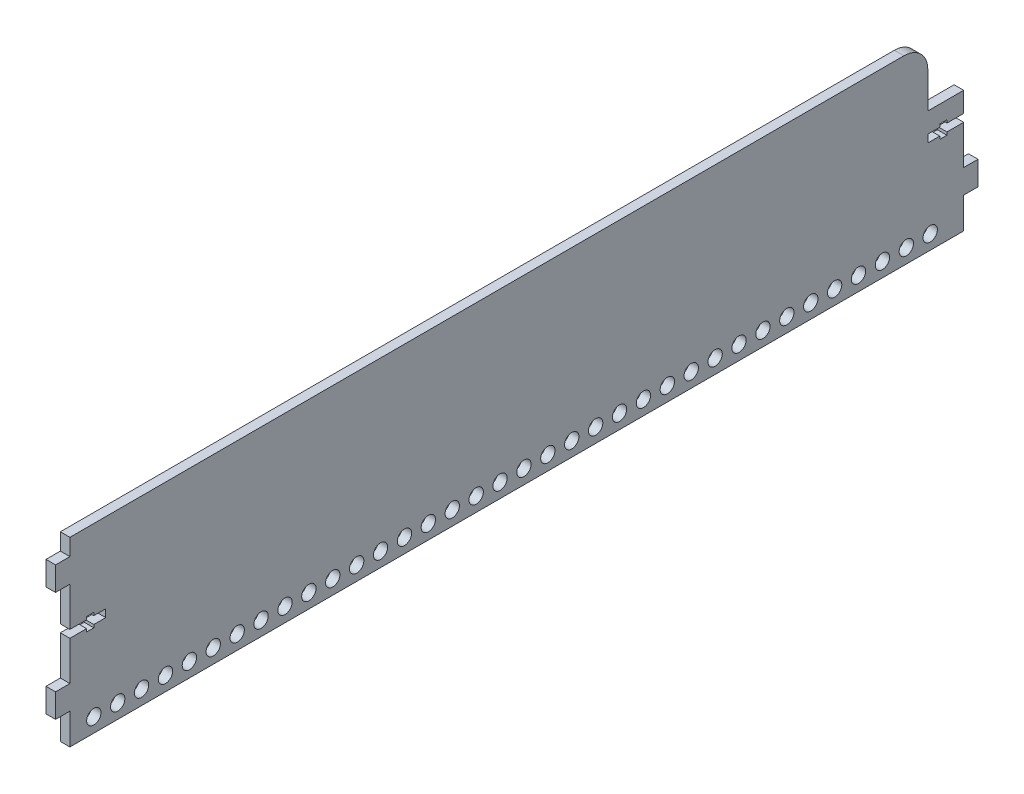
SolidWorks part; units mm, degrees
ref_plane "Front Plane" through (0, 0, 0) normal (0, 0, 1) x (1, 0, 0)
ref_plane "Top Plane" through (0, 0, 0) normal (0, 1, 0) x (1, 0, 0)
ref_plane "Right Plane" through (0, 0, 0) normal (1, 0, 0) x (0, 0, -1)
sketch "Sketch1" plane through (0, 0, 0) normal (1, 0, 0) x (0, 0, -1)
  line L1 (-187, -40) -> (187, -40)
  line L2 (-187, -40) -> (-187, 40)
  line L3 (-187, 40) -> (187, 40)
  line L4 (187, -40) -> (187, 40)
  line L5 (-187, -40) -> (187, 40) construction
  line L6 (-187, 40) -> (187, -40) construction
  point P0 (0, 0)
  dimension "D1" = 80
  dimension "D2" = 374
extrude "Boss-Extrude1" add sketch "Sketch1" along normal blind 4
sketch "Sketch4" plane through (0, 0, 187) normal (0, 0, 1) x (1, 0, 0)
  line L1 (4, 29) -> (0, 29) construction
  line L2 (4, 19) -> (4, 29) construction
  line L3 (0, 29) -> (0, 19) construction
  line L4 (0, 19) -> (4, 19) construction
  line L7 (4, -17) -> (0, -17) construction
  line L8 (4, -27) -> (4, -17) construction
  line L9 (0, -17) -> (0, -27) construction
  line L10 (0, -27) -> (4, -27) construction
  line L13 (4, 29) -> (0, 29)
  line L14 (4, 19) -> (4, 29)
  line L15 (0, 29) -> (0, 19)
  line L16 (0, 19) -> (4, 19)
  line L17 (4, -17) -> (0, -17)
  line L18 (4, -27) -> (4, -17)
  line L19 (0, -17) -> (0, -27)
  line L20 (0, -27) -> (4, -27)
extrude "Boss-Extrude2" add sketch "Sketch4" along normal blind 6
sketch "Sketch5" plane through (0, 0, 0) normal (-1, 0, 0) x (0, 0, 1)
  line L0 (187, 19) -> (187, -17) construction
  line L7 (0, 0) -> (0, -20.5925) construction
  line L8 (-187, 2.6) -> (-180, 2.6)
  line L9 (-177, 3.8) -> (-180, 3.8)
  line L10 (-177, 2.6) -> (-172, 2.6)
  line L11 (-172, -0.6) -> (-172, 2.6)
  line L12 (-177, -0.6) -> (-172, -0.6)
  line L13 (-177, -1.8) -> (-180, -1.8)
  line L14 (-187, -0.6) -> (-180, -0.6)
  line L15 (-180, -1.8) -> (-180, -0.6)
  line L16 (-180, 2.6) -> (-180, 3.8)
  line L17 (-177, 2.6) -> (-177, 3.8)
  line L18 (-177, -1.8) -> (-177, -0.6)
  line L19 (193, -0.6) -> (193, 2.6) construction
  line L20 (193, -0.6) -> (193, 2.6)
  line L21 (193, 1) -> (146.4296, 1) construction
  line L25 (187, -0.6) -> (187, 2.6)
  line L26 (177, -1.8) -> (177, -0.6)
  line L27 (177, 2.6) -> (177, 3.8)
  line L28 (180, 2.6) -> (180, 3.8)
  line L29 (180, -1.8) -> (180, -0.6)
  line L30 (187, -0.6) -> (180, -0.6)
  line L31 (177, -1.8) -> (180, -1.8)
  line L32 (177, -0.6) -> (172, -0.6)
  line L33 (172, -0.6) -> (172, 2.6)
  line L34 (177, 2.6) -> (172, 2.6)
  line L35 (177, 3.8) -> (180, 3.8)
  line L36 (187, 2.6) -> (180, 2.6)
  line L37 (-187, -0.6) -> (-187, 2.6)
  line L38 (-193, -0.6) -> (-193, 2.6)
  point P0 (187, 1)
  dimension "D1" = 15
  dimension "D2" = 5.6
  dimension "D3" = 3.2
  dimension "D4" = 7
  dimension "D5" = 3
extrude "Cut-Extrude3" cut sketch "Sketch5" against normal up to next contours L25 L36 L28 L35 L27 L34 L33 L32 L26 L31 L29 L30 | L37 L14 L15 L13 L18 L12 L11 L10 L17 L9 L16 L8 region at (0, 1, -179.3696) region at (0, 1, 179.3696)
sketch "Sketch7" plane through (0, 0, -187) normal (0, 0, -1) x (-1, 0, 0)
  line L6 (-4, -17) -> (0, -17)
  line L7 (-4, -17) -> (-4, -27)
  line L8 (-4, -27) -> (0, -27)
  line L9 (0, -17) -> (0, -27)
  line L15 (-4, -40) -> (-4, -0.6) construction
  line L16 (0, -40) -> (0, -0.6) construction
  line L17 (-4, -17) -> (0, -17) construction
  line L18 (0, -27) -> (-4, -27) construction
extrude "Boss-Extrude3" add sketch "Sketch7" along normal blind 6
sketch "Sketch8" plane through (0, 40, 0) normal (0, 1, 0) x (1, 0, 0)
  line L1 (0, 187) -> (4, 187)
  line L2 (0, 187) -> (0, -187)
  line L3 (0, -187) -> (4, -187)
  line L4 (4, 187) -> (4, -187)
extrude "Cut-Extrude4" cut sketch "Sketch8" against normal blind 4
sketch "Sketch9" plane through (0, 36, 0) normal (0, 1, 0) x (1, 0, 0)
  line L0 (0, 187) -> (0, -187) construction
  line L1 (0, 187) -> (4, 187)
  line L2 (0, 187) -> (0, 172)
  line L3 (0, 172) -> (4, 172)
  line L4 (4, 187) -> (4, 172)
  line L5 (4, -187) -> (4, 187) construction
  dimension "D2" = 15
extrude "Cut-Extrude5" cut sketch "Sketch9" against normal blind 25
fillet "Fillet1" radius 10 1 edges at (2, 36, -172)
sketch "Sketch10" plane through (0, 0, 0) normal (-1, 0, 0) x (0, 0, 1)
  line L0 (187, -40) -> (-187, -40) construction
  line L1 (187, -27) -> (187, -40) construction
  circle A0 centre (177, -34) radius 3
  circle A1 centre (167, -34) radius 3
  circle A2 centre (157, -34) radius 3
  circle A3 centre (147, -34) radius 3
  circle A4 centre (137, -34) radius 3
  circle A5 centre (127, -34) radius 3
  circle A6 centre (117, -34) radius 3
  circle A7 centre (107, -34) radius 3
  circle A8 centre (97, -34) radius 3
  circle A9 centre (87, -34) radius 3
  circle A10 centre (77, -34) radius 3
  circle A11 centre (67, -34) radius 3
  circle A12 centre (57, -34) radius 3
  circle A13 centre (47, -34) radius 3
  circle A14 centre (37, -34) radius 3
  circle A15 centre (27, -34) radius 3
  circle A16 centre (17, -34) radius 3
  circle A17 centre (7, -34) radius 3
  circle A18 centre (-3, -34) radius 3
  circle A19 centre (-13, -34) radius 3
  circle A20 centre (-23, -34) radius 3
  circle A21 centre (-33, -34) radius 3
  circle A22 centre (-43, -34) radius 3
  circle A23 centre (-53, -34) radius 3
  circle A24 centre (-63, -34) radius 3
  circle A25 centre (-73, -34) radius 3
  circle A26 centre (-83, -34) radius 3
  circle A27 centre (-93, -34) radius 3
  circle A28 centre (-103, -34) radius 3
  circle A29 centre (-113, -34) radius 3
  circle A30 centre (-123, -34) radius 3
  circle A31 centre (-133, -34) radius 3
  circle A32 centre (-143, -34) radius 3
  circle A33 centre (-153, -34) radius 3
  circle A34 centre (-163, -34) radius 3
  circle A35 centre (-173, -34) radius 3
  dimension "D1" = 6
  dimension "D2" = 6
  dimension "D3" = 10
  dimension "D4" = 36
extrude "Cut-Extrude6" cut sketch "Sketch10" against normal up to next (4 mm away)
